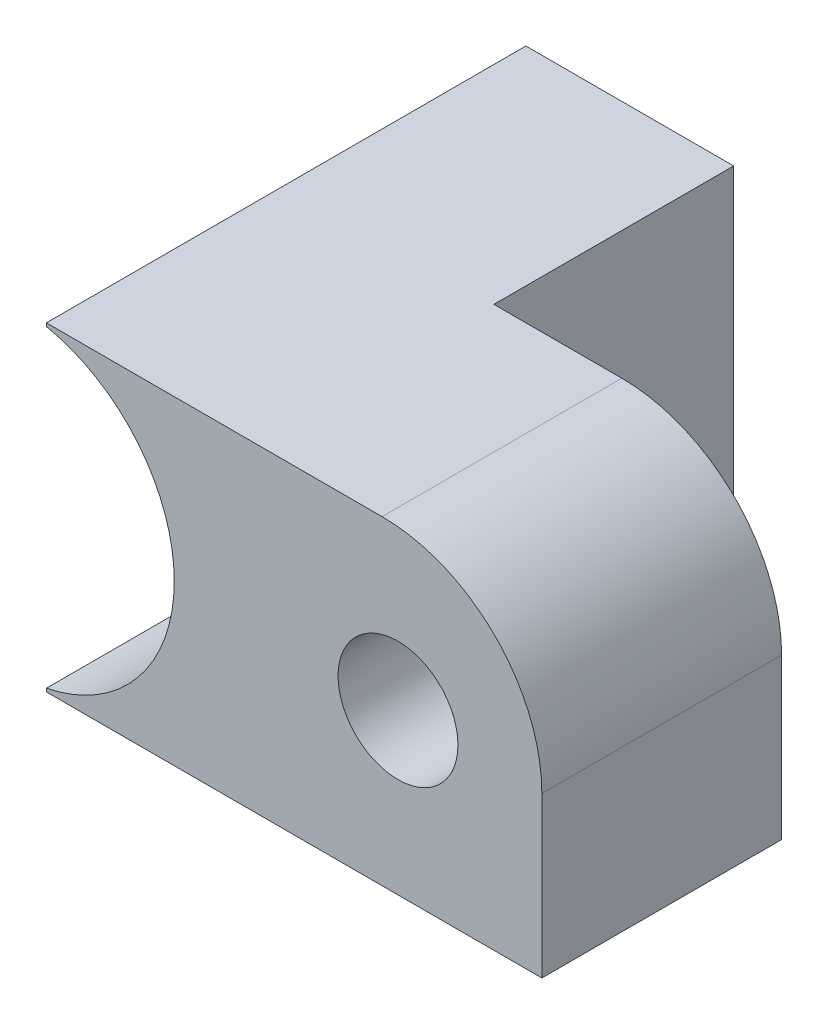
SolidWorks part; units mm, degrees
material "AISI Type A2 Tool Steel Custom"
ref_plane "Front Plane" through (0, 0, 0) normal (0, 0, 1) x (1, 0, 0)
ref_plane "Top Plane" through (0, 0, 0) normal (0, 1, 0) x (1, 0, 0)
ref_plane "Right Plane" through (0, 0, 0) normal (1, 0, 0) x (0, 0, -1)
sketch "Sketch1" plane through (0, 0, 0) normal (0, 0, 1) x (1, 0, 0)
  line L1 (2.54, 0) -> (41.91, 0)
  line L3 (2.54, 25.4) -> (29.21, 25.4)
  line L4 (41.91, 0) -> (41.91, 12.7)
  line L5 (2.54, 25.4) -> (2.54, 25.1434)
  line L8 (2.54, 0.2566) -> (2.54, 0)
  arc A1 (2.54, 0.2566) -> (2.54, 25.1434) centre (0, 12.7) ccw
  arc A2 (41.91, 12.7) -> (29.21, 25.4) centre (29.21, 12.7) ccw
  point P6 (35.6806, 10.2806)
  point P12 (40.1314, 13.0818)
  dimension "D2" = 25.4
  dimension "D3" = 12.7
  dimension "D1" = 41.91
  dimension "D4" = 2.54
  dimension "D7" = 0.2566
extrude "Boss-Extrude1" add sketch "Sketch1" along normal blind 38.1
sketch "Sketch2" plane through (0, 0, 0) normal (0, 0, -1) x (-1, 0, 0)
  line L0 (-19.05, 0) -> (-19.05, 25.4)
  line L3 (-2.54, 0) -> (-41.91, 0) construction
  line L4 (-29.21, 25.4) -> (-2.54, 25.4) construction
  line L8 (-19.05, 0) -> (-41.91, 0)
  line L9 (-29.21, 25.4) -> (-2.54, 25.4) construction
  line L11 (-41.91, 0) -> (-41.91, 12.7) construction
  line L13 (-41.91, 0) -> (-41.91, 12.7)
  line L14 (-29.21, 25.4) -> (-19.05, 25.4)
  arc A0 (-29.21, 25.4) -> (-41.91, 12.7) centre (-29.21, 12.7) ccw construction
  arc A2 (-29.21, 25.4) -> (-41.91, 12.7) centre (-29.21, 12.7) ccw
  dimension "D1" = 19.05
extrude "Cut-Extrude1" cut sketch "Sketch2" against normal blind 19.05
sketch "Sketch3" plane through (0, 0, 38.1) normal (0, 0, 1) x (1, 0, 0)
  line L0 (2.54, 0) -> (41.91, 0) construction
  line L1 (41.91, 0) -> (41.91, 12.7) construction
  point P0 (30.48, 12.7)
  dimension "D1" = 12.7
  dimension "D2" = 11.43
hole_wizard "3/8 (0.375) Diameter Hole1" positions "Sketch3" profile "Sketch4" hole size "3/8" standard "ANSI Inch" end condition through all
sketch "Sketch4" plane through (30.48, 12.7, 38.1) normal (1, 0, 0) x (0, -1, 0)
  line L0 (0, 0) -> (0, 38.1)
  line L1 (0, 38.1) -> (4.7625, 38.1)
  line L2 (4.7625, 38.1) -> (4.7625, 0)
  line L5 (4.7625, 0) -> (0, 0)
  line L11 (0, -6.35) -> (0, 107.95) construction
  dimension "Thru Hole Dia." = 9.525
  dimension "Thru Hole Depth" = 38.1
chamfer "Chamfer1" distance 1.27 angle 45 1 edges at (19.05, 0, 9.525)
